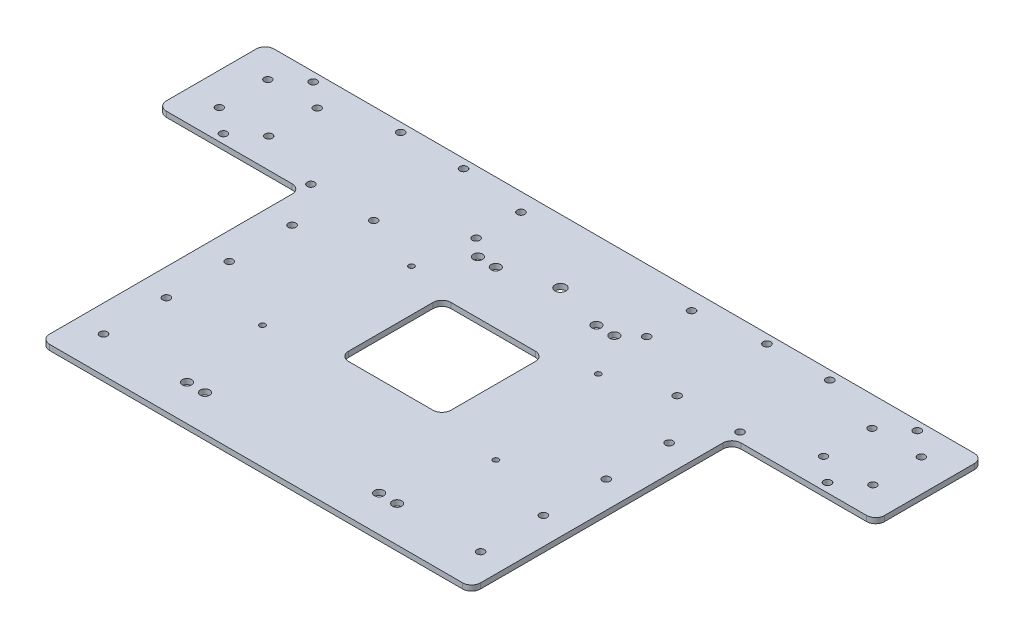
SolidWorks part; units mm, degrees
material "Thornel Mat VMA"
ref_plane "前视基准面" through (0, 0, 0) normal (0, 0, 1) x (1, 0, 0)
ref_plane "上视基准面" through (0, 0, 0) normal (0, 1, 0) x (1, 0, 0)
ref_plane "右视基准面" through (0, 0, 0) normal (1, 0, 0) x (0, 0, -1)
sketch "草图1" plane through (0, 0, 0) normal (0, 1, 0) x (1, 0, 0)
  line L0 (35.5759, -158.8718) -> (35.5759, 46.1282) construction
  line L1 (-164.4241, -13.8718) -> (235.5759, -13.8718)
  line L2 (-164.4241, -13.8718) -> (-164.4241, 46.1282)
  line L3 (-164.4241, 46.1282) -> (235.5759, 46.1282)
  line L4 (235.5759, -13.8718) -> (235.5759, 46.1282)
  line L5 (-11.9241, 36.1282) -> (83.0759, 36.1282) construction
  line L6 (-11.9241, 11.1282) -> (83.0759, 11.1282) construction
  line L7 (-84.4241, -158.8718) -> (155.5759, -158.8718)
  line L8 (-84.4241, -158.8718) -> (-84.4241, -13.8718)
  line L9 (-84.4241, -13.8718) -> (155.5759, -13.8718)
  line L10 (155.5759, -158.8718) -> (155.5759, -13.8718)
  line L11 (25.0759, 10.6282) -> (46.0759, 10.6282) construction
  line L12 (25.0759, 0.1282) -> (46.0759, 0.1282) construction
  line L13 (25.0759, 0.1282) -> (25.0759, 21.1282) construction
  line L14 (25.0759, 21.1282) -> (46.0759, 21.1282) construction
  line L15 (46.0759, 0.1282) -> (46.0759, 21.1282) construction
  line L16 (7.0759, -55.3718) -> (64.0759, -55.3718) construction
  line L17 (7.0759, -26.8718) -> (64.0759, -26.8718)
  line L18 (7.0759, -26.8718) -> (7.0759, -83.8718)
  line L19 (7.0759, -83.8718) -> (64.0759, -83.8718)
  line L20 (64.0759, -26.8718) -> (64.0759, -83.8718)
  line L21 (35.5759, 21.1282) -> (35.5759, 0.1282) construction
  circle A0 centre (-11.9241, 36.1282) radius 2.1
  circle A1 centre (-11.9241, 11.1282) radius 2.1
  circle A2 centre (83.0759, 11.1282) radius 2.1
  circle A3 centre (83.0759, 36.1282) radius 2.1
  circle A8 centre (35.5759, 10.6282) radius 3.05
  point P0 (0, 0)
  point P6 (0, -121.2547)
  point P16 (35.5759, 36.1282)
  point P19 (35.5759, 11.1282)
  point P23 (35.5759, 5.0732)
  point P30 (35.5759, -28.1434)
  point P35 (35.5759, -26.8718)
  dimension "D8" = 21
  dimension "D13" = 6.1
  dimension "D14" = 10.5
  dimension "D15" = 4.2
  dimension "D1" = 400
  dimension "D2" = 60
  dimension "D3" = 145
  dimension "D4" = 240
  dimension "D5" = 10
  dimension "D6" = 95
  dimension "D7" = 25
  dimension "D9" = 189.5
  dimension "D10" = 27
  dimension "D11" = 15
  dimension "D12" = 57
extrude "构型与裁判孔" add sketch "草图1" along normal blind 3 contours L1 L4 L3 L2 A3 L15 L12 L13 L14 A0 A1 A2 | L7 L10 L1 L8 region at (35.5759, 0, -16.1176) region at (35.5759, 0, 89.564)
sketch "草图2" plane through (0, 3, 0) normal (0, 1, 0) x (1, 0, 0)
  line L0 (-164.4241, 16.1282) -> (235.5759, 16.1282) construction
  line L1 (-164.4241, -13.8718) -> (-164.4241, 46.1282) construction
  line L2 (235.5759, -13.8718) -> (235.5759, 46.1282) construction
  line L3 (35.5759, 46.1282) -> (35.5759, -158.8718) construction
  line L4 (-164.4241, 46.1282) -> (235.5759, 46.1282) construction
  line L5 (-84.4241, -158.8718) -> (155.5759, -158.8718) construction
  line L6 (-146.4241, 2.6282) -> (-146.4241, 29.6282) construction
  line L7 (-118.9241, 2.6282) -> (-118.9241, 29.6282) construction
  line L8 (-146.4241, 29.6282) -> (-118.9241, 29.6282) construction
  line L9 (-48.9241, -8.8718) -> (-48.9241, 41.1282) construction
  line L10 (-132.6741, 29.6282) -> (-132.6741, 46.1282) construction
  line L11 (-132.6741, 41.1282) -> (-83.9241, 41.1282) construction
  circle A0 centre (-146.4241, 29.6282) radius 2.05
  circle A1 centre (-146.4241, 2.6282) radius 2.05
  circle A2 centre (-118.9241, 29.6282) radius 2.05
  circle A3 centre (-118.9241, 2.6282) radius 2.05
  circle A4 centre (-48.9241, 41.1282) radius 2.1
  circle A5 centre (-83.9241, 41.1282) radius 2.1
  circle A6 centre (-48.9241, -8.8718) radius 2.1
  circle A7 centre (-83.9241, -8.8718) radius 2.1
  circle A8 centre (-132.6741, 41.1282) radius 2.1
  circle A9 centre (-132.6741, -8.8718) radius 2.1
  circle A10 centre (203.8259, -8.8718) radius 2.1
  circle A11 centre (203.8259, 41.1282) radius 2.1
  circle A12 centre (155.0759, -8.8718) radius 2.1
  circle A13 centre (120.0759, -8.8718) radius 2.1
  circle A14 centre (155.0759, 41.1282) radius 2.1
  circle A15 centre (120.0759, 41.1282) radius 2.1
  circle A16 centre (190.0759, 2.6282) radius 2.05
  circle A17 centre (190.0759, 29.6282) radius 2.05
  circle A18 centre (217.5759, 2.6282) radius 2.05
  circle A19 centre (217.5759, 29.6282) radius 2.05
  point P15 (-146.4241, 16.1282)
  point P20 (-118.9241, 16.1282)
  point P25 (-48.9241, 16.1282)
  dimension "D2" = 4.1
  dimension "D4" = 5
  dimension "D5" = 4.2
  dimension "D7" = 2
  dimension "D8" = 18
  dimension "D1" = 27
  dimension "D3" = 45.5
  dimension "D6" = 70
extrude "切除-拉伸1" cut sketch "草图2" against normal through all
fillet "圆角1" radius 5 12 edges at (155.5759, 1.5, 13.8718) (-84.4241, 1.5, 13.8718) (235.5759, 1.5, -46.1282) (235.5759, 1.5, 13.8718) (155.5759, 1.5, 158.8718) (-84.4241, 1.5, 158.8718) (-164.4241, 1.5, -46.1282) (-164.4241, 1.5, 13.8718) (7.0759, 1.5, 83.8718) (64.0759, 1.5, 83.8718) (64.0759, 1.5, 26.8718) (7.0759, 1.5, 26.8718)
sketch "草图3" plane through (0, 3, 0) normal (0, 1, 0) x (1, 0, 0)
  line L0 (-89.4241, -13.8718) -> (160.5759, -13.8718) construction
  line L1 (-69.4241, -13.8718) -> (-69.4241, -158.8718) construction
  line L2 (-79.4241, -158.8718) -> (150.5759, -158.8718) construction
  line L3 (35.5759, 46.1282) -> (35.5759, -158.8718) construction
  line L4 (-159.4241, 46.1282) -> (230.5759, 46.1282) construction
  line L5 (-84.4241, -153.8718) -> (-84.4241, -18.8718) construction
  line L6 (7.0759, -55.3718) -> (64.0759, -55.3718) construction
  line L7 (190.0759, 2.6282) -> (-118.9241, 2.6282) construction
  line L8 (-16.4241, -20.3718) -> (-29.4241, -20.3718) construction
  line L9 (-48.9617, -13.8718) -> (-48.9617, -158.8718) construction
  line L10 (-79.4241, -158.8718) -> (150.5759, -158.8718) construction
  line L11 (-84.4241, -153.8718) -> (-84.4241, -18.8718) construction
  line L12 (-16.4241, -20.3718) -> (-16.4241, -90.3718) construction
  line L13 (-16.4241, -90.3718) -> (-29.4241, -90.3718) construction
  line L14 (-29.4241, -20.3718) -> (-29.4241, -90.3718) construction
  line L15 (-22.9241, -90.3718) -> (-22.9241, -20.3718) construction
  line L16 (-16.4241, -55.3718) -> (-29.4241, -55.3718) construction
  line L17 (7.0759, -31.8718) -> (7.0759, -78.8718) construction
  line L18 (-69.4241, -138.8718) -> (140.5759, -138.8718) construction
  circle A0 centre (-69.4241, -33.8718) radius 2.1
  circle A1 centre (-69.4241, -68.8718) radius 2.1
  circle A2 centre (-69.4241, -103.8718) radius 2.1
  circle A3 centre (-69.4241, -138.8718) radius 2.1
  circle A4 centre (140.5759, -138.8718) radius 2.1
  circle A5 centre (140.5759, -103.8718) radius 2.1
  circle A6 centre (140.5759, -68.8718) radius 2.1
  circle A7 centre (140.5759, -33.8718) radius 2.1
  circle A8 centre (-16.4241, -20.3718) radius 1.55
  circle A9 centre (-29.4241, -90.3718) radius 1.55
  circle A10 centre (100.5759, -90.3718) radius 1.55
  circle A11 centre (87.5759, -20.3718) radius 1.55
  circle A12 centre (-2.4241, 2.6282) radius 2.6
  circle A13 centre (7.5759, 2.6282) radius 2.6
  circle A14 centre (63.5759, 2.6282) radius 2.6
  circle A15 centre (73.5759, 2.6282) radius 2.6
  circle A16 centre (-22.9241, -138.8718) radius 2.6
  circle A17 centre (-12.9241, -138.8718) radius 2.6
  circle A18 centre (84.0759, -138.8718) radius 2.6
  circle A19 centre (94.0759, -138.8718) radius 2.6
  point P44 (7.0759, -55.3718)
  point P495 (-22.9241, -55.3718)
  dimension "D1" = 20
  dimension "D2" = 35
  dimension "D3" = 35
  dimension "D4" = 35
  dimension "D7" = 3.1
  dimension "D10" = 5.2
  dimension "D11" = 10
  dimension "D12" = 28
  dimension "D14" = 10
  dimension "D5" = 15
  dimension "D6" = 35.4624
  dimension "D8" = 13
  dimension "D9" = 70
  dimension "D13" = 20
  dimension "D15" = 40
extrude "切除-拉伸2" cut sketch "草图3" against normal through all
